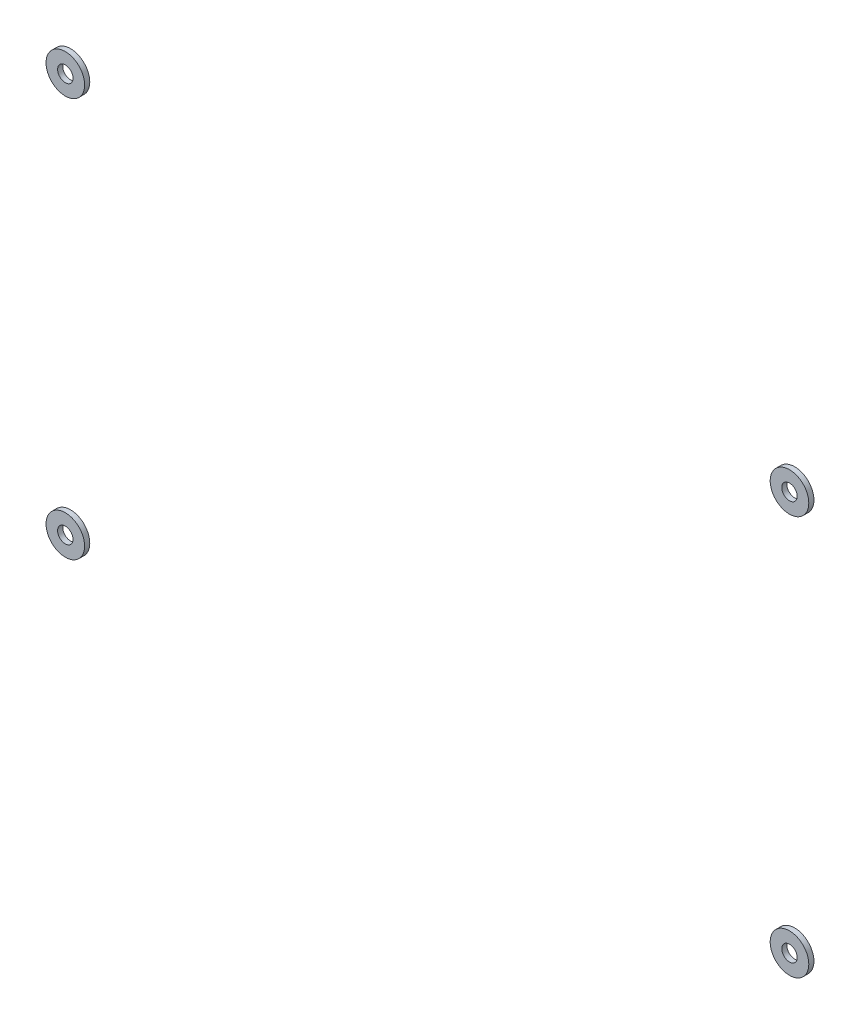
SolidWorks part; units mm, degrees
ref_plane "Front Plane" through (0, 0, 0) normal (0, 0, 1) x (1, 0, 0)
ref_plane "Top Plane" through (0, 0, 0) normal (0, 1, 0) x (1, 0, 0)
ref_plane "Right Plane" through (0, 0, 0) normal (1, 0, 0) x (0, 0, -1)
sketch "Sketch1" plane through (0, 0, 0) normal (0, 0, 1) x (1, 0, 0)
  circle A0 centre (-56.3, 78.45) radius 3
extrude "Boss-Extrude1" add sketch "Sketch1" along normal blind 0.8 from offset 70.7
sketch "Sketch2" plane through (0, 0, 0) normal (0, 0, 1) x (1, 0, 0)
  circle A0 centre (-56.3, 78.45) radius 1.2
extrude "Boss-Extrude2" add sketch "Sketch2" along normal blind 3 from offset 70.1 separate body
combine bodies "Combine1" operation type subtract main body 101 bodies to subtract 102
sketch "Sketch3" plane through (0, 0, 0) normal (0, 0, 1) x (1, 0, 0)
  circle A0 centre (-56.3, 140.55) radius 3
extrude "Boss-Extrude3" add sketch "Sketch3" along normal blind 0.8 from offset 70.7
sketch "Sketch4" plane through (0, 0, 0) normal (0, 0, 1) x (1, 0, 0)
  circle A0 centre (-56.3, 140.55) radius 1.2
extrude "Boss-Extrude4" add sketch "Sketch4" along normal blind 3 from offset 70.1 separate body
combine bodies "Combine2" operation type subtract main body 104 bodies to subtract 105
sketch "Sketch5" plane through (0, 0, 0) normal (0, 0, 1) x (1, 0, 0)
  circle A0 centre (56.3, 78.45) radius 3
extrude "Boss-Extrude5" add sketch "Sketch5" along normal blind 0.8 from offset 70.7
sketch "Sketch6" plane through (0, 0, 0) normal (0, 0, 1) x (1, 0, 0)
  circle A0 centre (56.3, 78.45) radius 1.2
extrude "Boss-Extrude6" add sketch "Sketch6" along normal blind 3 from offset 70.1 separate body
combine bodies "Combine3" operation type subtract main body 107 bodies to subtract 108
sketch "Sketch7" plane through (0, 0, 0) normal (0, 0, 1) x (1, 0, 0)
  circle A0 centre (56.3, 140.55) radius 3
extrude "Boss-Extrude7" add sketch "Sketch7" along normal blind 0.8 from offset 70.7
sketch "Sketch8" plane through (0, 0, 0) normal (0, 0, 1) x (1, 0, 0)
  circle A0 centre (56.3, 140.55) radius 1.2
extrude "Boss-Extrude8" add sketch "Sketch8" along normal blind 3 from offset 70.1 separate body
combine bodies "Combine4" operation type subtract main body 110 bodies to subtract 111
